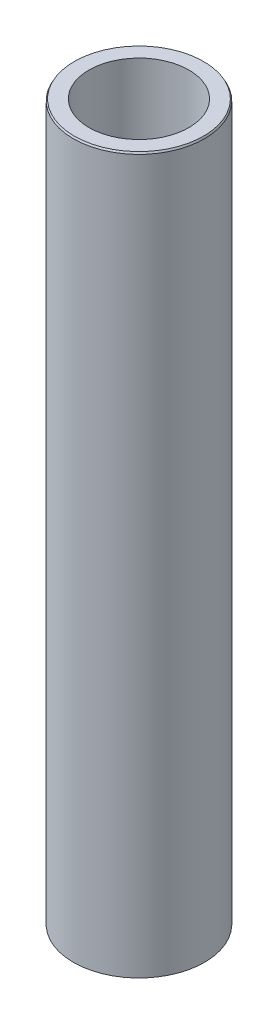
SolidWorks part; units mm, degrees
ref_plane "Front Plane" through (0, 0, 0) normal (0, 0, 1) x (1, 0, 0)
ref_plane "Top Plane" through (0, 0, 0) normal (0, 1, 0) x (1, 0, 0)
ref_plane "Right Plane" through (0, 0, 0) normal (1, 0, 0) x (0, 0, -1)
sketch "Sketch1" plane through (0, 0, 0) normal (0, 1, 0) x (1, 0, 0)
  circle A0 centre (0, 0) radius 55
  dimension "SHAFT_OD" = 110
extrude "Boss-Extrude1" add sketch "Sketch1" along normal blind 600
sketch "Sketch2" plane through (0, 0, 0) normal (0, 1, 0) x (1, 0, 0)
  circle A0 centre (0, 0) radius 41.8463
  dimension "BORE_D" = 83.6926
extrude "Cut-Extrude1" cut sketch "Sketch2" along normal through all
chamfer "Chamfer1" distance 1.4718 angle 28.837 2 edges at (0, 600, 55) (0, 0, 55) first distance on face at (0, 600, 55) first distance on face at (0, 0, 41.8463)
